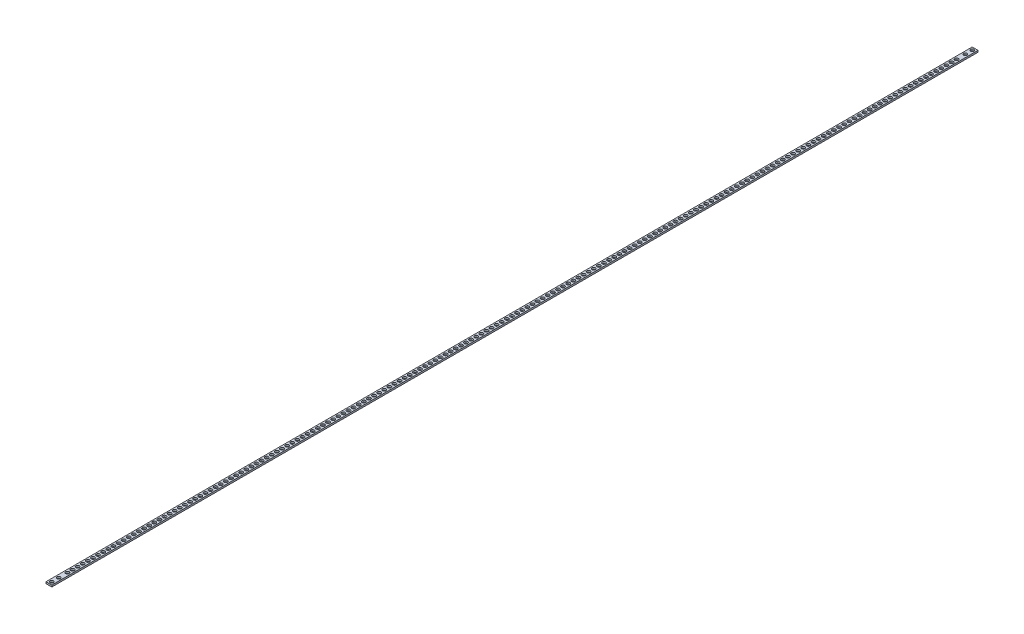
SolidWorks part; units mm, degrees
ref_plane "Front Plane" through (0, 0, 0) normal (0, 0, 1) x (1, 0, 0)
ref_plane "Top Plane" through (0, 0, 0) normal (0, 1, 0) x (1, 0, 0)
ref_plane "Right Plane" through (0, 0, 0) normal (1, 0, 0) x (0, 0, -1)
sketch "Sketch1" plane through (0, 0, 0) normal (0, 1, 0) x (1, 0, 0)
  line L0 (0, 0) -> (0, 1600)
  line L1 (0, 0) -> (10, 0)
  line L2 (0, 1600) -> (10, 1600)
  line L3 (10, 0) -> (10, 1600)
  dimension "Rail Length" = 1600
  dimension "Rail Width" = 10
extrude "Boss-Extrude1" add sketch "Sketch1" along normal blind 3
sketch "Sketch11" plane through (0, 3, 0) normal (0, 1, 0) x (1, 0, 0)
  line L0 (0, 0) -> (10, 0) construction
  line L1 (0, 1600) -> (0, 0) construction
  line L2 (10, 1600) -> (0, 1600) construction
  line L3 (10, 0) -> (10, 1600) construction
  point P0 (5, 5)
  point P6 (5, 1595)
  dimension "B End Spacing ~ Feature Holes" = 5
  dimension "B Centre on Rail ~ Feature Holes" = 5
  dimension "A End Spacing ~ Feature Holes" = 5
  dimension "A Centre on Rail ~ Feature Holes" = 5
hole_wizard "Tap Drill for M7x1.0 Tap1" positions "Sketch12" profile "Sketch13" hole size "M7x1.0" standard "ISO" end condition through all
sketch "Sketch12" plane through (0, 0, 0) normal (0, -1, 0) x (-1, 0, 0)
  point P0 (-5, 5)
sketch "Sketch13" plane through (5, 0, -5) normal (1, 0, 0) x (0, 0, -1)
  line L0 (0, 0) -> (0, 3)
  line L1 (0, 3) -> (3, 3)
  line L2 (3, 3) -> (3, 0.025)
  line L3 (3, 0.025) -> (3.025, 0)
  line L5 (3.025, 0) -> (0, 0)
  line L6 (-3, 0.025) -> (-3.025, 0) construction
  line L11 (0, -6.35) -> (0, 107.95) construction
  dimension "Thru Hole Dia." = 6
  dimension "Thru Hole Depth" = 3
  dimension "Near C'Sink Dia." = 6.05
  dimension "Near C'Sink Angle" = 90
pattern_linear "LPattern2" count 2 spacing 12 along (0, 0, -1) of "Tap Drill for M7x1.0 Tap1"
hole_wizard "Tap Drill for M7x1.0 Tap2" positions "Sketch14" profile "Sketch15" hole size "M7x1.0" standard "ISO" end condition through all
sketch "Sketch14" plane through (0, 0, 0) normal (0, -1, 0) x (-1, 0, 0)
  point P0 (-5, 1595)
sketch "Sketch15" plane through (5, 0, -1595) normal (1, 0, 0) x (0, 0, -1)
  line L0 (0, 0) -> (0, 3)
  line L1 (0, 3) -> (3, 3)
  line L2 (3, 3) -> (3, 0.025)
  line L3 (3, 0.025) -> (3.025, 0)
  line L5 (3.025, 0) -> (0, 0)
  line L6 (-3, 0.025) -> (-3.025, 0) construction
  line L11 (0, -6.35) -> (0, 107.95) construction
  dimension "Thru Hole Dia." = 6
  dimension "Thru Hole Depth" = 3
  dimension "Near C'Sink Dia." = 6.05
  dimension "Near C'Sink Angle" = 90
pattern_linear "LPattern3" count 2 spacing 12 along (0, 0, 1) of "Tap Drill for M7x1.0 Tap2"
sketch "Sketch8" plane through (0, 3, 0) normal (0, 1, 0) x (1, 0, 0)
  line L0 (0, 0) -> (10, 0) construction
  line L1 (10, 0) -> (10, 1600) construction
  point P0 (5, 32)
  dimension "Dist. from End" = 32
  dimension "Centre on Rail" = 5
hole_wizard "Ø6.0mm Dowel Hole1" positions "Sketch9" profile "Sketch10" hole size "Ø6.0" standard "ISO" end condition through all
sketch "Sketch9" plane through (0, 3, 0) normal (0, 1, 0) x (1, 0, 0)
  point P0 (5, 32)
sketch "Sketch10" plane through (5, 3, -32) normal (1, 0, 0) x (0, 0, 1)
  line L0 (0, 0) -> (0, 3)
  line L1 (0, 3) -> (3, 3)
  line L2 (3, 3) -> (3, 0.025)
  line L3 (3, 0.025) -> (3.025, 0)
  line L5 (3.025, 0) -> (0, 0)
  line L6 (-3, 0.025) -> (-3.025, 0) construction
  line L11 (0, -6.35) -> (0, 107.95) construction
  dimension "Thru Hole Dia." = 6
  dimension "Thru Hole Depth" = 3
  dimension "Near C'Sink Dia." = 6.05
  dimension "Near C'Sink Angle" = 90
pattern_linear "LPattern1" count 175 spacing 8.8276 along (0, 0, -1) of "Ø6.0mm Dowel Hole1"
equation "\"Rail Length\"= 1600"
equation "\"Rail Width\"= 10"
equation "\"Rail Thickness\"= 3"
equation "\"Number of Holes\"= 175"
equation "\"Feature Hole Spacing from End\"= 5"
equation "\"Number of Feature Holes\"= 2"
equation "\"Spacing of Feature Holes\"= 12"
equation "\"Rail Length@Sketch1\"= \"Rail Length\""
equation "\"Rail Width@Sketch1\"= \"Rail Width\""
equation "\"Rail Thickness@Boss-Extrude1\"= \"Rail Thickness\""
equation "\"No. Holes@LPattern1\"= \"Number of Holes\""
equation "\"Dist. from End@Sketch8\" = \"Feature Hole Spacing from End\" + ( \"Number of Feature Holes\" * \"Spacing of Feature Holes\" ) + ( \"Thru Hole Dia.@Sketch10\" / 2 )"
equation "\"Centre on Rail@Sketch8\" = \"Rail Width@Sketch1\" / 2"
equation "\"Hole Spacing@LPattern1\"= ( \"Rail Length@Sketch1\" - ( 2 * \"Dist. from End@Sketch8\" ) ) / ( \"No. Holes@LPattern1\" - 1 )"
equation "\"A Centre on Rail ~ Feature Holes@Sketch11\"= \"Rail Width@Sketch1\" / 2"
equation "\"B Centre on Rail ~ Feature Holes@Sketch11\" = \"A Centre on Rail ~ Feature Holes@Sketch11\""
equation "\"A End Spacing ~ Feature Holes@Sketch11\" = \"Feature Hole Spacing from End\""
equation "\"B End Spacing ~ Feature Holes@Sketch11\"= \"A End Spacing ~ Feature Holes@Sketch11\""
equation "\"A Hole Spacing ~ Feature Holes@LPattern3\"= \"Spacing of Feature Holes\""
equation "\"B Hole Spacing ~ Feature Holes@LPattern2\"= \"Spacing of Feature Holes\""
equation "\"D1@LPattern2\" = \"Number of Feature Holes\""
equation "\"D1@LPattern3\"= \"D1@LPattern2\""
